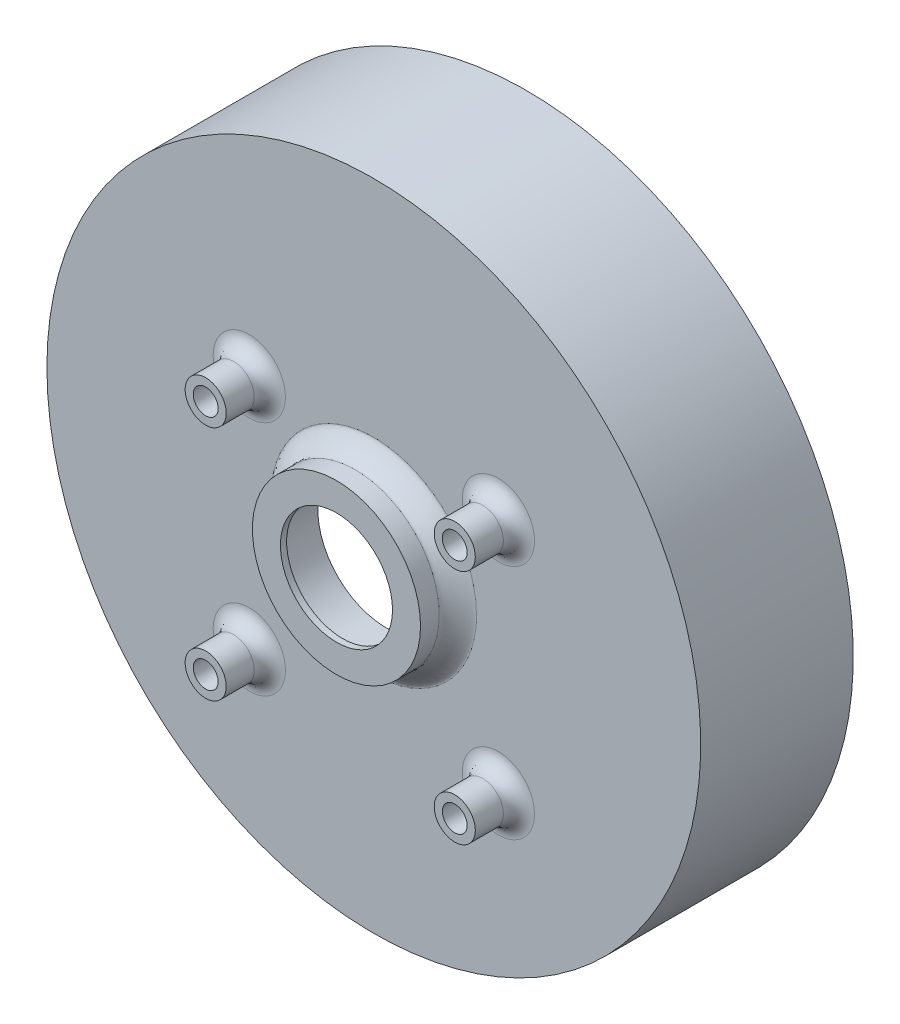
SolidWorks part; units mm, degrees
ref_plane "Front Plane" through (0, 0, 0) normal (0, 0, 1) x (1, 0, 0)
ref_plane "Top Plane" through (0, 0, 0) normal (0, 1, 0) x (1, 0, 0)
ref_plane "Right Plane" through (0, 0, 0) normal (1, 0, 0) x (0, 0, -1)
sketch "Sketch1" plane through (0, 0, 0) normal (0, 0, 1) x (1, 0, 0)
  circle A0 centre (0, 0) radius 45
  circle A1 centre (0, 0) radius 52.5
  circle A2 centre (0, 0) radius 11
  dimension "D1" = 90
  dimension "D2" = 105
  dimension "D3" = 22
extrude "Boss-Extrude1" add sketch "Sketch1" along normal blind 22.5 contours A1 A0 region at (-51.0151, 0, 0)
sketch "Sketch2" plane through (0, 0, 0) normal (0, 0, 1) x (1, 0, 0)
  line L0 (-20, 15) -> (20, 15) construction
  line L1 (-20, -23) -> (20, -23) construction
  line L2 (-20, 18) -> (20, 18)
  line L3 (-16, -35) -> (16, -35)
  line L4 (-23, 15) -> (-23, -23)
  line L5 (23, 15) -> (23, -23)
  line L6 (-27.3518, -23) -> (-27.3518, -29) construction
  line L7 (-27.3518, -29) -> (-27.3518, -35) construction
  line L8 (-27.3518, -29) -> (32.2638, -29) construction
  line L9 (-27.3518, -35) -> (32.2638, -35) construction
  line L10 (-16, -35) -> (-16, -29)
  line L11 (16, -35) -> (16, -29)
  line L12 (-20.8734, -26.0636) -> (-17.0471, -27.4916)
  line L13 (0, 21.7483) -> (0, -55.2269) construction
  line L15 (20.8734, -26.0636) -> (17.0471, -27.4916)
  circle A0 centre (0, 0) radius 3.2
  circle A1 centre (20, 15) radius 1.25
  circle A2 centre (-20, 15) radius 1.25
  circle A3 centre (-20, -23) radius 1.25
  circle A4 centre (20, -23) radius 1.25
  arc A5 (-20, 18) -> (-23, 15) centre (-20, 15) ccw
  arc A6 (23, 15) -> (20, 18) centre (20, 15) ccw
  arc A8 (-16, -29) -> (-17.0471, -27.4916) centre (-17.61, -29) ccw
  arc A9 (16, -29) -> (17.0471, -27.4916) centre (17.61, -29) cw
  arc A11 (-23, -23) -> (-20.8734, -26.0636) centre (-19.73, -23) ccw
  arc A12 (23, -23) -> (20.8734, -26.0636) centre (19.73, -23) cw
  point P5 (0, 15)
  point P10 (0, -23)
  point P18 (0, -35)
  dimension "D1" = 15
  dimension "D3" = 2.5
  dimension "D4" = 2.5
  dimension "D7" = 2.5
  dimension "D8" = 2.5
  dimension "D11" = 6
  dimension "D9" = 6
  dimension "D12" = 6.4
  dimension "D15" = 3.27
  dimension "D16" = 1.61
  dimension "D2" = 40
  dimension "D5" = 40
  dimension "D6" = 23
  dimension "D10" = 32
  dimension "D13" = 6
  dimension "D14" = 6
  dimension "D17" = 7.3518
extrude "Boss-Extrude2" add sketch "Sketch1<2>" along normal blind 2 from surface contours A1 A0 | A0 region at (-43.7272, 0, 0) region at (-51.0151, 0, 0) starting at face at (45, 0, 22.5)
sketch "Sketch1<2>" plane through (0, 0, 0) normal (0, 0, 1) x (1, 0, 0) same geometry as "Sketch1"
sketch "Sketch3" plane through (0, 0, 24.5) normal (0, 0, 1) x (1, 0, 0)
  circle A0 centre (-20, -23) radius 1.25 construction
  circle A1 centre (20, -23) radius 1.25 construction
  circle A2 centre (20, 15) radius 1.25 construction
  circle A3 centre (-20, 15) radius 1.25 construction
  circle A4 centre (-20, -23) radius 1.25 construction
  circle A5 centre (20, -23) radius 1.25 construction
  circle A6 centre (20, 15) radius 1.25 construction
  circle A7 centre (-20, 15) radius 1.25 construction
  circle A8 centre (-20, 15) radius 2
  circle A9 centre (20, 15) radius 2
  circle A10 centre (20, -23) radius 2
  circle A11 centre (-20, -23) radius 2
  circle A12 centre (-20, 15) radius 3.3
  circle A13 centre (20, 15) radius 3.3
  circle A14 centre (20, -23) radius 3.3
  circle A15 centre (-20, -23) radius 3.3
  dimension "D1" = 4
  dimension "D2" = 6.6
extrude "Boss-Extrude3" add sketch "Sketch3" along normal blind 7
fillet "Fillet1" radius 2.5 4 edges at (-16.7, -23, 24.5) (23.3, -23, 24.5) (23.3, 15, 24.5) (-16.7, 15, 24.5) conic radius 2.5
sketch "Sketch4" plane through (0, 0, 24.5) normal (0, 0, 1) x (1, 0, 0)
  circle A0 centre (0, 0) radius 13.5
  circle A1 centre (0, 0) radius 11
  circle M7 centre (0, 0) radius 11
  dimension "D1" = 27
extrude "Boss-Extrude4" add sketch "Sketch4" along normal blind 6 contours A0 M7 region at (-13.1182, 0, 24.5)
sketch "Sketch5" plane through (0, 0, 22.5) normal (0, 0, -1) x (-1, 0, 0)
  circle A0 centre (0, 0) radius 9
  circle A1 centre (0, 0) radius 11
  dimension "D1" = 18
extrude "Boss-Extrude5" add sketch "Sketch5" along normal blind 1 from surface starting at face at (11, 0, 30.5)
sketch "Sketch7" plane through (0, 0, 0) normal (0, 0, -1) x (-1, 0, 0)
  circle A0 centre (0, 0) radius 48.75 construction
  circle A1 centre (-34.4715, 34.4715) radius 2.1
  circle A2 centre (34.4715, 34.4715) radius 2.1
  circle A3 centre (34.4715, -34.4715) radius 2.1
  circle A4 centre (-34.4715, -34.4715) radius 2.1
  point P14 (0, 0)
  dimension "D1" = 97.5
  dimension "D2" = 4.2
  dimension "D3" = 4
extrude "Cut-Extrude1" cut sketch "Sketch7" against normal blind 10
fillet "Fillet2" radius 3 1 edges at (13.5, 0, 24.5) conic radius 10
